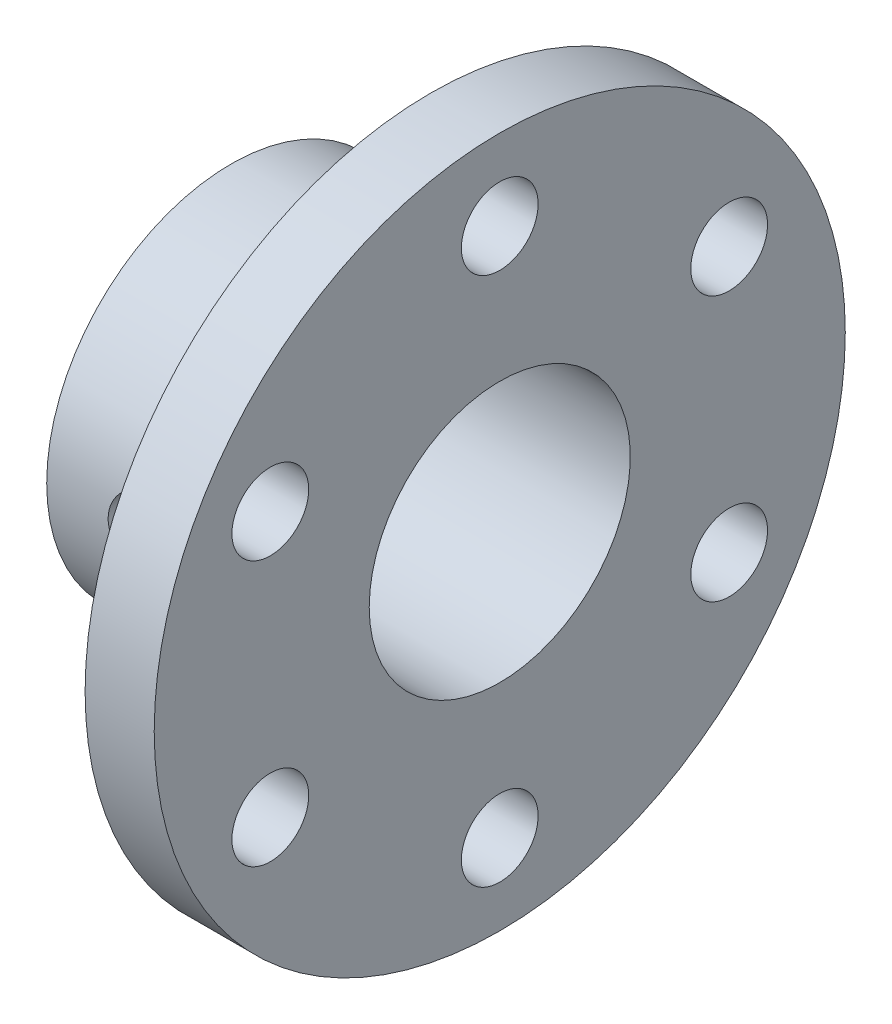
SolidWorks part; units mm, degrees
ref_plane "Front Plane" through (0, 0, 0) normal (0, 0, 1) x (1, 0, 0)
ref_plane "Top Plane" through (0, 0, 0) normal (0, 1, 0) x (1, 0, 0)
ref_plane "Right Plane" through (0, 0, 0) normal (1, 0, 0) x (0, 0, -1)
sketch "Sketch1" plane through (0, 0, 0) normal (0, 0, 1) x (1, 0, 0)
  line L0 (-11.6129, 0) -> (15.7189, 0) construction
  line L1 (-14.7005, 4.5) -> (-14.7005, 12)
  line L2 (-14.7005, 12) -> (-1.7005, 12)
  line L3 (-1.7005, 12) -> (-1.7005, 22.5)
  line L4 (-1.7005, 22.5) -> (2.7995, 22.5)
  line L5 (2.7995, 22.5) -> (2.7995, 4.5)
  line L6 (2.7995, 4.5) -> (-14.7005, 4.5)
  dimension "D1" = 4.5
  dimension "D2" = 4.5
  dimension "D3" = 13
  dimension "D5" = 12
revolve "Revolve1" add sketch "Sketch1" angle 360 about L0
sketch "Sketch2" plane through (-1.7005, 0, 0) normal (-1, 0, 0) x (0, 0, 1)
  line L0 (0, -17.25) -> (0, 17.25) construction
  line L1 (-14.9389, 8.625) -> (14.9389, -8.625) construction
  line L2 (14.9389, 8.625) -> (-14.9389, -8.625) construction
  circle A0 centre (0, 0) radius 17.25 construction
  circle A9 centre (0, 17.25) radius 2.5
  circle A10 centre (14.9389, 8.625) radius 2.5
  circle A11 centre (14.9389, -8.625) radius 2.5
  circle A12 centre (0, -17.25) radius 2.5
  circle A13 centre (-14.9389, -8.625) radius 2.5
  circle A14 centre (-14.9389, 8.625) radius 2.5
  point P22 (0, 0)
  dimension "D1" = 34.5
  dimension "D2" = 60
  dimension "D4" = 5
  dimension "D3" = 60
  dimension "D5" = 6
extrude "Cut-Extrude1" cut sketch "Sketch2" against normal up to surface (4.5 mm away) up to face at (2.7995, 0, 22.5)
ref_plane "Plane1" through (0, 0, 12) normal (0, 0, 1) x (1, 0, 0)
sketch "Sketch3" plane through (0, 0, 12) normal (0, 0, 1) x (1, 0, 0)
  line L0 (-14.7005, 0) -> (-1.7005, 0) construction
  line L1 (-14.7005, 12) -> (-14.7005, -12) construction
  line L2 (-1.7005, 22.5) -> (-1.7005, -22.5) construction
  circle A0 centre (-8.2005, 0) radius 2.5
  dimension "D1" = 5
extrude "Cut-Extrude2" cut sketch "Sketch3" against normal up to surface (7.5 mm away) up to face at (2.7995, 0, 4.5)
sketch "Sketch4" plane through (-14.7005, 0, 0) normal (-1, 0, 0) x (0, 0, 1)
  circle A0 centre (0, 0) radius 8.5
extrude "Cut-Extrude3" cut sketch "Sketch4" against normal blind 20
